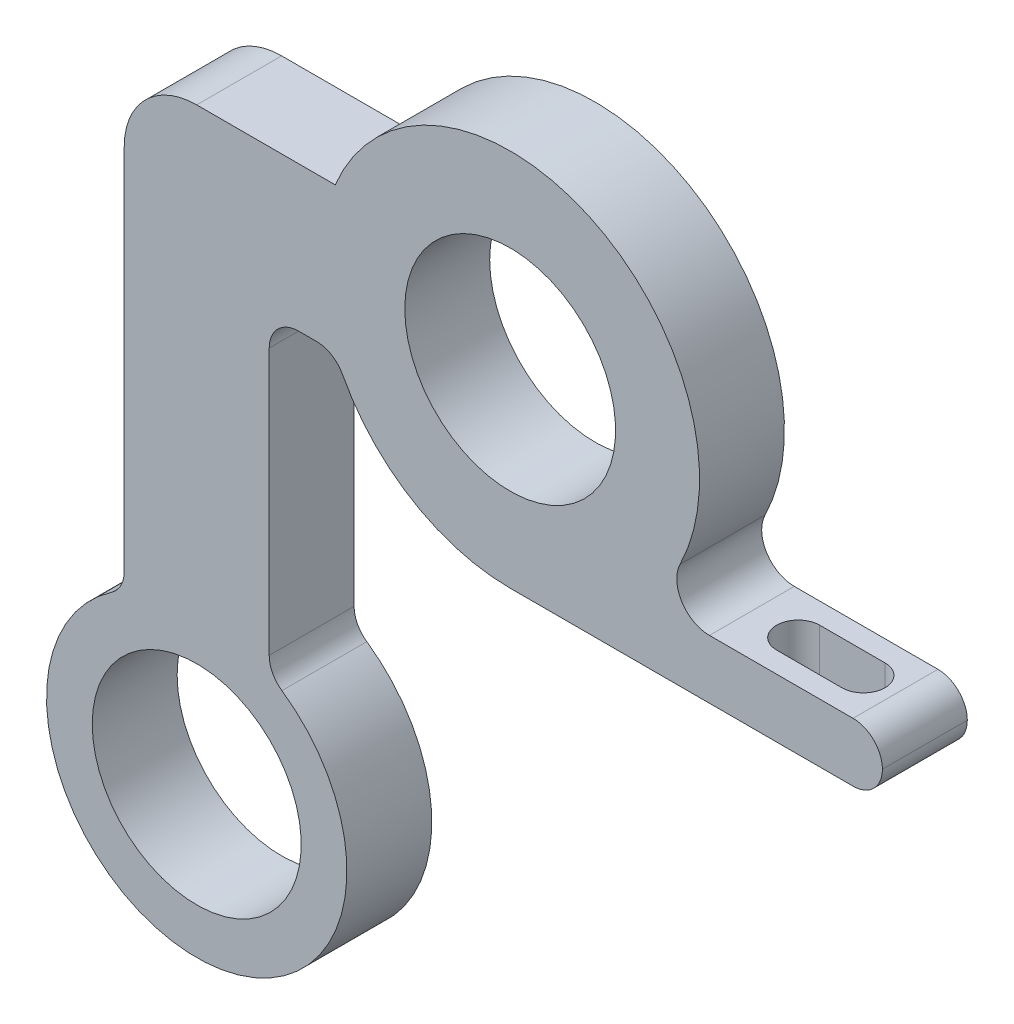
SolidWorks part; units mm, degrees
ref_plane "Front Plane" through (0, 0, 0) normal (0, 0, 1) x (1, 0, 0)
ref_plane "Top Plane" through (0, 0, 0) normal (0, 1, 0) x (1, 0, 0)
ref_plane "Right Plane" through (0, 0, 0) normal (1, 0, 0) x (0, 0, -1)
sketch "Sketch1" plane through (0, 0, 0) normal (0, 0, 1) x (1, 0, 0)
  line L0 (0, 0) -> (0, 39.5) construction
  line L1 (-5.55, 0) -> (-5.55, 39.5)
  line L2 (5.55, 0) -> (5.55, 39.5)
  line L3 (0, 39.5) -> (24, 39.5) construction
  line L4 (0, 45.05) -> (24, 45.05)
  line L5 (0, 33.95) -> (24, 33.95)
  line L6 (24, 25) -> (52.5, 25)
  line L7 (52.5, 25) -> (52.5, 29.5)
  line L8 (52.5, 29.5) -> (34.5, 29.5)
  line L9 (45.3, 29.5) -> (45.3, 25)
  line L10 (48.3, 29.5) -> (48.3, 25)
  line L11 (42.3, 29.5) -> (42.3, 25)
  line L12 (42.3, 27.25) -> (48.3, 27.25) construction
  circle A0 centre (0, 0) radius 2.55
  arc A1 (-5.55, 0) -> (5.55, 0) centre (0, 0) ccw
  arc A2 (5.55, 39.5) -> (-5.55, 39.5) centre (0, 39.5) ccw
  arc A3 (0, 45.05) -> (0, 33.95) centre (0, 39.5) ccw
  arc A4 (24, 33.95) -> (24, 45.05) centre (24, 39.5) ccw
  circle A5 centre (24, 39.5) radius 8.07
  circle A6 centre (24, 39.5) radius 14.5
  circle A7 centre (0, 0) radius 8
  circle A8 centre (0, 0) radius 11.5
  point P3 (0, 19.75)
  point P9 (12, 39.5)
  point P34 (45.3, 27.25)
  dimension "D1" = 5.1
  dimension "D5" = 16.14
  dimension "D6" = 29
  dimension "D7" = 16
  dimension "D8" = 23
  dimension "D2" = 3
  dimension "D3" = 39.5
  dimension "D4" = 24
  dimension "D9" = 4.5
  dimension "D10" = 21.3
  dimension "D11" = 18
  dimension "D12" = 6
extrude "Boss-Extrude3" add sketch "Sketch1" along normal blind 6.5 contours A3 L1 A1 L2 L5 A0 | A2 A3 L5 L2 | A6 L4 A2 L2 L5 | L4 A6 L5 A5 | L5 A6 L4 A5 | L1 A8 L2 A7 | L2 A8 L1 A7 | A6 L6 L11 L8 | L8 L11 L6 L9 | L10 L8 L9 L6 | L8 L10 L6 L7 region at (-3.2539, -7.6523, 0) region at (0, 9.1362, 0) region at (-0.1092, 22.8111, 0) region at (0.2756, 39.2244, 0) region at (7.305, 40.023, 0) region at (26.7509, 53.3266, 0) region at (13.2644, 39.5, 0) region at (36.5072, 26.972, 0) region at (43.8, 27.25, 0) region at (46.8, 27.25, 0) region at (50.4, 27.25, 0)
sketch "Sketch2" plane through (0, 29.5, 0) normal (0, 1, 0) x (1, 0, 0)
  line L0 (45.3, 0) -> (45.3, -6.5) construction
  line L1 (52.5, -6.5) -> (34.5, -6.5) construction
  line L2 (42.8, -3.25) -> (47.8, -3.25) construction
  line L3 (42.8, -1.6) -> (47.8, -1.6)
  line L4 (42.8, -4.9) -> (47.8, -4.9)
  arc A1 (42.8, -1.6) -> (42.8, -4.9) centre (42.8, -3.25) ccw
  arc A2 (47.8, -4.9) -> (47.8, -1.6) centre (47.8, -3.25) ccw
  point P7 (45.3, -3.25)
  dimension "D2" = 1.65
  dimension "D1" = 5
extrude "Cut-Extrude1" cut sketch "Sketch2" against normal blind 16
fillet "Fillet1" radius 2.5 1 edges at (34.5, 29.5, 3.25)
fillet "Fillet2" radius 2.25 6 edges at (10.6042, 33.95, 3.25) (-5.55, 10.0721, 3.25) (5.55, 10.0721, 3.25) (5.55, 33.95, 3.25) (52.5, 25, 3.25) (52.5, 29.5, 3.25)
